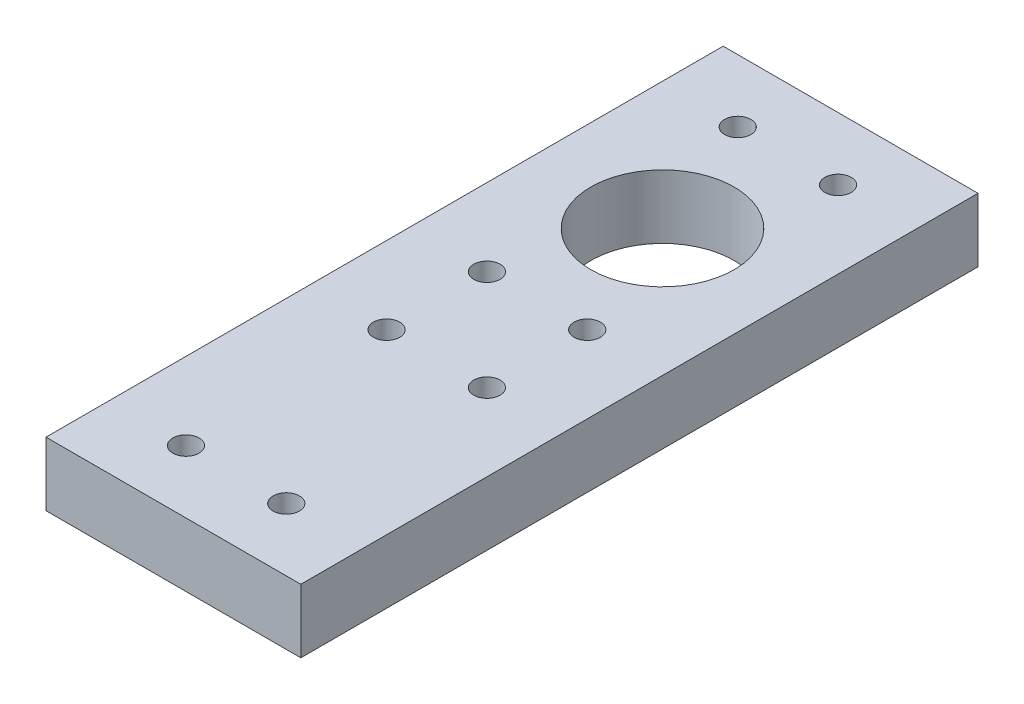
SolidWorks part; units mm, degrees
ref_plane "Front Plane" through (0, 0, 0) normal (0, 0, 1) x (1, 0, 0)
ref_plane "Top Plane" through (0, 0, 0) normal (0, 1, 0) x (1, 0, 0)
ref_plane "Right Plane" through (0, 0, 0) normal (1, 0, 0) x (0, 0, -1)
sketch "Sketch2" plane through (0, 0, 0) normal (0, 1, 0) x (1, 0, 0)
  line L1 (0, 0) -> (101.6, 0)
  line L2 (0, 0) -> (0, 270)
  line L3 (0, 270) -> (101.6, 270)
  line L4 (101.6, 0) -> (101.6, 270)
  dimension "D1" = 101.6
  dimension "D2" = 270
extrude "Boss-Extrude1" add sketch "Sketch2" along normal blind 25.4
sketch "Sketch3" plane through (0, 25.4, 0) normal (0, 1, 0) x (1, 0, 0)
  line L1 (0, 270) -> (50.8, 270)
  line L2 (0, 270) -> (0, 195)
  line L3 (0, 195) -> (50.8, 195)
  line L4 (50.8, 270) -> (50.8, 195)
  line L5 (30.8, 245) -> (70.8, 245)
  line L6 (30.8, 245) -> (30.8, 145)
  line L7 (30.8, 145) -> (70.8, 145)
  line L8 (70.8, 245) -> (70.8, 145)
  line L9 (30.8, 245) -> (70.8, 145) construction
  line L10 (30.8, 145) -> (70.8, 245) construction
  circle A0 centre (70.8, 245) radius 5.25
  circle A1 centre (30.8, 245) radius 5.25
  circle A2 centre (70.8, 145) radius 5.25
  circle A3 centre (30.8, 145) radius 5.25
  circle A4 centre (50.8, 195) radius 28.575
  dimension "D1" = 50.8
  dimension "D2" = 75
  dimension "D3" = 40
  dimension "D4" = 100
extrude "Cut-Extrude1" cut sketch "Sketch3" against normal blind 25.4 contours A1 | A0 | A4 | A2 | A3
sketch "Sketch4" plane through (0, 25.4, 0) normal (0, 1, 0) x (1, 0, 0)
  line L1 (0, 270) -> (50.8, 270)
  line L2 (0, 270) -> (0, 65)
  line L3 (0, 65) -> (50.8, 65)
  line L4 (50.8, 270) -> (50.8, 65)
  line L5 (30.8, 25) -> (70.8, 25)
  line L6 (30.8, 25) -> (30.8, 105)
  line L7 (30.8, 105) -> (70.8, 105)
  line L8 (70.8, 25) -> (70.8, 105)
  line L9 (30.8, 25) -> (70.8, 105) construction
  line L10 (30.8, 105) -> (70.8, 25) construction
  circle A0 centre (70.8, 105) radius 5.25
  circle A1 centre (30.8, 105) radius 5.25
  circle A2 centre (30.8, 25) radius 5.25
  circle A3 centre (70.8, 25) radius 5.25
  dimension "D1" = 50.8
  dimension "D2" = 205
  dimension "D3" = 40
  dimension "D4" = 80
extrude "Cut-Extrude2" cut sketch "Sketch4" against normal blind 25.4 contours A1 | A0 | A3 | A2
